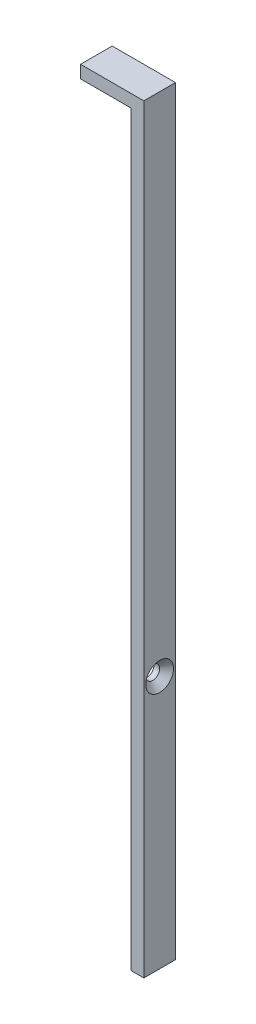
SolidWorks part; units mm, degrees
ref_plane "Front Plane" through (0, 0, 0) normal (0, 0, 1) x (1, 0, 0)
ref_plane "Top Plane" through (0, 0, 0) normal (0, 1, 0) x (1, 0, 0)
ref_plane "Right Plane" through (0, 0, 0) normal (1, 0, 0) x (0, 0, -1)
sketch "Sketch1" plane through (0, 0, 0) normal (0, 0, 1) x (1, 0, 0)
  line L0 (-8, 0) -> (0, 0)
  line L1 (0, 0) -> (0, -118)
  line L2 (0, -118) -> (2, -118)
  line L3 (2, -118) -> (2, 2)
  line L4 (2, 2) -> (-8, 2)
  line L5 (-8, 2) -> (-8, 0)
  point P5 (-10, 2)
  point P8 (2, -118)
  point P9 (2, 2)
  point P10 (-10, 2)
  dimension "D1" = 2
  dimension "D2" = 10
  dimension "D3" = 120
extrude "Boss-Extrude1" add sketch "Sketch1" along normal blind 5
sketch "Sketch2" plane through (2, 0, 0) normal (1, 0, 0) x (0, 0, -1)
  line L0 (-2.5, 2) -> (-2.5, -78) construction
  line L1 (-5, 2) -> (0, 2) construction
  point P5 (-2.5, -78)
  dimension "D1" = 80
hole_wizard "CSK for M2 Flat Head Machine Screw1" positions "3DSketch1" profile "Sketch3" countersink size "M2" standard "ANSI Metric" end condition up to next
sketch3d "3DSketch1"
  point P0 (2, -78, 2.5)
sketch "Sketch3" plane through (2, -78, 2.5) normal (0, 1, 0) x (0, 0, -1)
  line L0 (0, 0) -> (0, 2)
  line L1 (0, 2) -> (1.1, 2)
  line L2 (1.1, 2) -> (1.1, 1.1)
  line L3 (1.1, 1.1) -> (2.2, 0)
  line L5 (2.2, 0) -> (0, 0)
  line L6 (-1.1, 1.1) -> (-2.2, 0) construction
  line L11 (0, -6.35) -> (0, 107.95) construction
  dimension "Thru Hole Dia." = 2.2
  dimension "Thru Hole Depth" = 2
  dimension "Near C'Sink Dia." = 4.4
  dimension "Near C'Sink Angle" = 90
